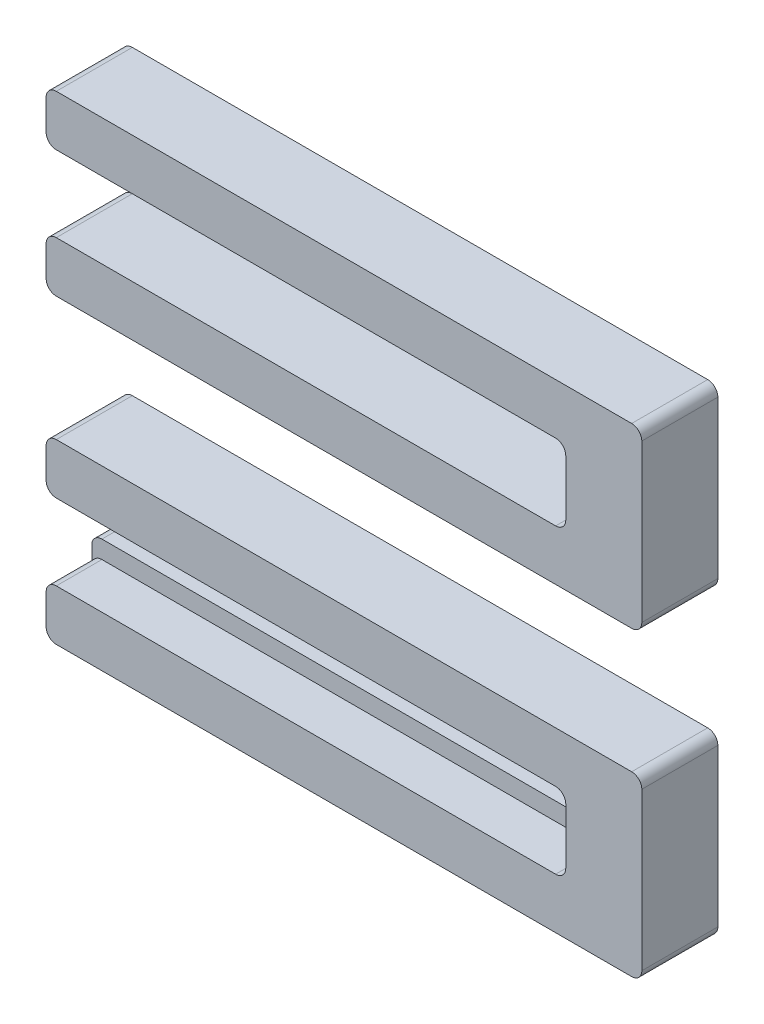
SolidWorks part; units mm, degrees
ref_plane "Front Plane" through (0, 0, 0) normal (0, 0, 1) x (1, 0, 0)
ref_plane "Top Plane" through (0, 0, 0) normal (0, 1, 0) x (1, 0, 0)
ref_plane "Right Plane" through (0, 0, 0) normal (1, 0, 0) x (0, 0, -1)
sketch "Sketch2" plane through (0, 0, 0) normal (0, 0, 1) x (1, 0, 0)
  line L0 (-2.7742, -2.4497) -> (31.3823, -2.4497) construction
  line L1 (0, 0) -> (23.5, 0)
  line L2 (0, 0) -> (0, 7)
  line L3 (0, 7) -> (23.5, 7)
  line L4 (23.5, 0) -> (23.5, 7)
  line L5 (0, 5) -> (20.5, 5)
  line L6 (0, 5) -> (0, 2)
  line L7 (0, 2) -> (20.5, 2)
  line L8 (20.5, 5) -> (20.5, 2)
  line L9 (0, 5) -> (20.5, 5)
  line L10 (0, 5) -> (0, 4.3)
  line L11 (0, 4.3) -> (20.5, 4.3)
  line L12 (20.5, 5) -> (20.5, 4.3)
  line L13 (20.5, -9.8995) -> (20.5, -9.1995)
  line L14 (0, -9.1995) -> (20.5, -9.1995)
  line L15 (0, -9.8995) -> (0, -9.1995)
  line L16 (0, -9.8995) -> (20.5, -9.8995)
  line L17 (20.5, -9.8995) -> (20.5, -6.8995)
  line L18 (0, -6.8995) -> (20.5, -6.8995)
  line L19 (0, -9.8995) -> (0, -6.8995)
  line L20 (0, -9.8995) -> (20.5, -9.8995)
  line L21 (23.5, -4.8995) -> (23.5, -11.8995)
  line L22 (0, -11.8995) -> (23.5, -11.8995)
  line L23 (0, -4.8995) -> (0, -11.8995)
  line L24 (0, -4.8995) -> (23.5, -4.8995)
  dimension "D1" = 7
  dimension "D2" = 3
  dimension "D3" = 2
  dimension "D4" = 3
  dimension "D5" = 20.5
  dimension "D6" = 2.3
extrude "Boss-Extrude1" add sketch "Sketch2" along normal blind 3 contours L5 L8 L7 L2 L1 L4 L3 | L24 L23 L18 L17 L13 L16 L22 L21 region at (0.2452, 1, 0) region at (20.7452, -9.5495, 0)
extrude "Boss-Extrude3" add sketch "Sketch2<4>" along normal blind 1.2 contours L15 L16 L13 L14 | L6 L11 L8 L5 region at (10.25, 4.65, 0) region at (10.25, -9.5495, 0)
sketch "Sketch2<4>" plane through (0, 0, 0) normal (0, 0, 1) x (1, 0, 0) same geometry as "Sketch2"
fillet "Fillet2" radius 0.4 10 edges at (0, 5, 2.1) (20.5, 2, 1.5) (20.5, 4.3, 0.6) (20.5, 5, 2.1) (23.5, 7, 1.5) (23.5, 0, 1.5) (0, 0, 1.5) (0, 2, 1.5) (0, 4.3, 0.6) (0, 7, 1.5)
fillet "Fillet3" radius 0.4 10 edges at (23.5, -11.8995, 1.5) (23.5, -4.8995, 1.5) (20.5, -6.8995, 1.5) (20.5, -9.8995, 2.1) (20.5, -9.1995, 0.6) (0, -11.8995, 1.5) (0, -9.8995, 2.1) (0, -9.1995, 0.6) (0, -4.8995, 1.5) (0, -6.8995, 1.5)
